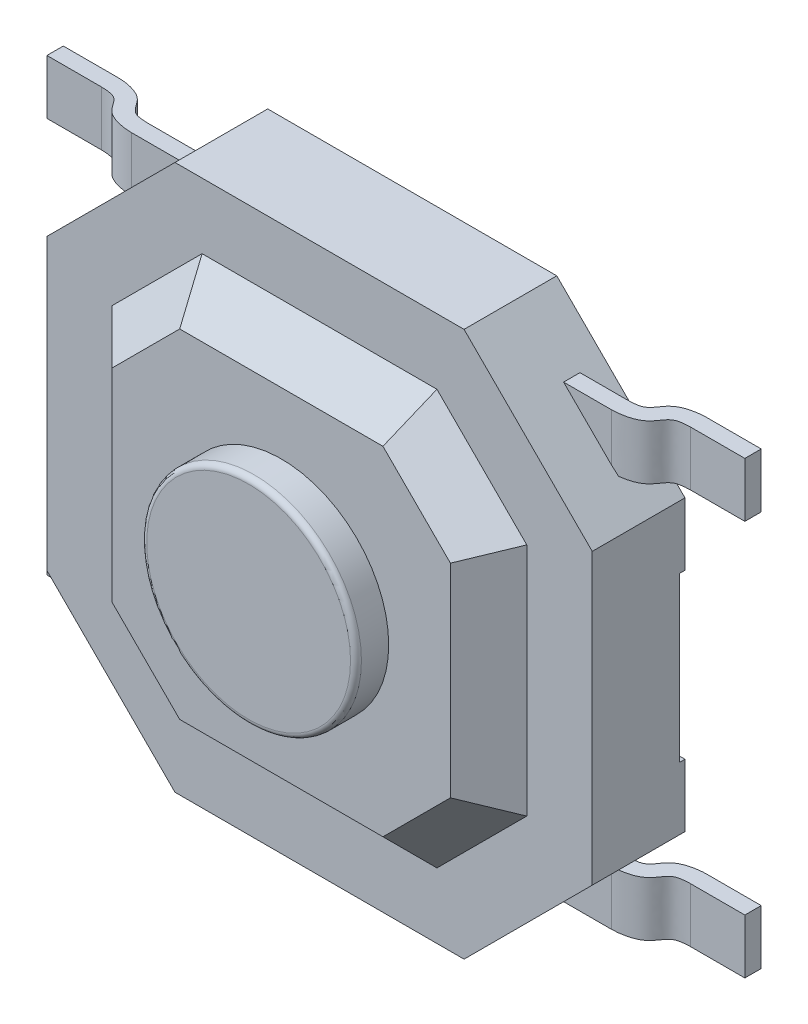
SolidWorks part; units mm, degrees
ref_plane "Front" through (0, 0, 0) normal (0, 0, 1) x (1, 0, 0)
ref_plane "Top" through (0, 0, 0) normal (0, 1, 0) x (1, 0, 0)
ref_plane "Right" through (0, 0, 0) normal (1, 0, 0) x (0, 0, -1)
ref_plane "Plane1" through (0, 0, 0) normal (0, 0, 1) x (1, 0, 0)
sketch "Sketch1" plane through (0, 0, 0) normal (0, 0, 1) x (1, 0, 0)
  line L0 (-1.3462, 2.54) -> (1.3462, 2.54)
  line L1 (1.3462, 2.54) -> (2.54, 1.3462)
  line L2 (2.54, 1.3462) -> (2.54, -1.3462)
  line L3 (2.54, -1.3462) -> (1.3462, -2.54)
  line L4 (1.3462, -2.54) -> (-1.3462, -2.54)
  line L5 (-1.3462, -2.54) -> (-2.54, -1.3462)
  line L6 (-2.54, -1.3462) -> (-2.54, 1.3462)
  line L7 (-2.54, 1.3462) -> (-1.3462, 2.54)
  line L8 (0, 2.54) -> (0, -2.54) construction
  point P10 (0, 0)
  dimension "D1" = 5.08
  dimension "D2" = 5.08
  dimension "D3" = 2.6924
extrude "Base" add sketch "Sketch1" along normal blind 0.8636
sketch "Sketch2" plane through (0, 0, 0.8636) normal (0, 0, 1) x (1, 0, 0)
  line L16 (-1.0937, 1.9304) -> (-1.9304, 1.0937)
  line L17 (-1.9304, 1.0937) -> (-1.9304, -1.0937)
  line L18 (-1.9304, -1.0937) -> (-1.0937, -1.9304)
  line L19 (-1.0937, -1.9304) -> (1.0937, -1.9304)
  line L20 (1.0937, -1.9304) -> (1.9304, -1.0937)
  line L21 (1.9304, -1.0937) -> (1.9304, 1.0937)
  line L22 (1.9304, 1.0937) -> (1.0937, 1.9304)
  line L23 (1.0937, 1.9304) -> (-1.0937, 1.9304)
  line L24 (-1.0937, 1.9304) -> (-1.9304, 1.0937)
  line L25 (-1.9304, 1.0937) -> (-1.9304, -1.0937)
  line L26 (-1.9304, -1.0937) -> (-1.0937, -1.9304)
  line L27 (-1.0937, -1.9304) -> (1.0937, -1.9304)
  line L28 (1.0937, -1.9304) -> (1.9304, -1.0937)
  line L29 (1.9304, -1.0937) -> (1.9304, 1.0937)
  line L30 (1.9304, 1.0937) -> (1.0937, 1.9304)
  line L31 (1.0937, 1.9304) -> (-1.0937, 1.9304)
  dimension "D1" = 0.6096
extrude "Tier1" add sketch "Sketch2" along normal blind 0.3556
chamfer "Chamfer1" distance 0.3556 angle 45 8 edges at (-1.512, 1.512, 1.2192) (0, 1.9304, 1.2192) (1.512, 1.512, 1.2192) (1.9304, 0, 1.2192) (1.512, -1.512, 1.2192) (0, -1.9304, 1.2192) (-1.512, -1.512, 1.2192) (-1.9304, 0, 1.2192) tangent propagation no
sketch "Sketch3" plane through (0, 0, 1.2192) normal (0, 0, 1) x (1, 0, 0)
  circle A0 centre (0, 0) radius 1
  dimension "D1" = 2
extrude "Button" add sketch "Sketch3" along normal blind 0.3048
fillet "ButtonC" radius 0.0508 1 edges at (1, 0, 1.524)
sketch "Sketch4" plane through (0, 0, 0) normal (0, 0, -1) x (-1, 0, 0)
  line L0 (2.54, 1.3462) -> (2.54, -1.3462) construction
  line L1 (2.54, -0.762) -> (-2.54, -0.762)
  line L2 (2.54, -0.762) -> (2.54, 0.762)
  line L3 (2.54, 0.762) -> (-2.54, 0.762)
  line L4 (-2.54, -0.762) -> (-2.54, 0.762)
  line L5 (-2.54, -1.3462) -> (-2.54, 1.3462) construction
  line L6 (0, -0.762) -> (0, 0.762) construction
  point P10 (0, 0)
  dimension "D1" = 1.524
extrude "Bottom cut" cut sketch "Sketch4" against normal blind 0.0508
sketch "Sketch6" plane through (0, -2.54, 0) normal (0, -1, 0) x (1, 0, 0)
  line L1 (-0.8382, 0.381) -> (-2.2352, 0.381)
  line L2 (-0.8382, 0.381) -> (-0.8382, 0.2286)
  line L3 (-0.8382, 0.2286) -> (-2.2352, 0.2286)
  line L4 (-2.2352, 0.381) -> (-2.2352, 0.2286)
  line L5 (-1.3462, 0) -> (1.3462, 0) construction
  line L6 (-1.3462, 0.8636) -> (-1.3462, 0) construction
  line L7 (-3.25, 0) -> (-2.742, 0)
  line L8 (-3.25, 0) -> (-3.25, 0.1524)
  line L9 (-3.25, 0.1524) -> (-2.742, 0.1524)
  line L10 (-2.742, 0) -> (-2.742, 0.1524)
  line L12 (-1.3462, 0.8636) -> (1.3462, 0.8636) construction
  line L13 (-3.0129, 0.0762) -> (-2.4711, 0.0762) construction
  line L14 (-2.5061, 0.3048) -> (-1.9643, 0.3048) construction
  spline S0 degree 3 poles (-2.2352, 0.3048) (-2.5739, 0.3048) (-2.4033, 0.0762) (-2.742, 0.0762) knots 0 0 0 0 1 1 1 1
  spline S1 degree 1 poles (-2.2352, 0.381) (-2.742, 0.1524) knots 0 0 1 1 construction
  spline S2 degree 3 poles (-2.2352, 0.381) (-2.3077, 0.381) (-2.477, 0.3473) (-2.5562, 0.2228) (-2.5912, 0.1832) (-2.642, 0.1591) (-2.7123, 0.1524) (-2.742, 0.1524) knots 0 0 0 0 0.25 0.5 0.75 0.875 1 1 1 1
  spline S3 degree 1 poles (-2.2352, 0.2286) (-2.742, 0) knots 0 0 1 1 construction
  spline S4 degree 3 poles (-2.2352, 0.2286) (-2.2649, 0.2286) (-2.3352, 0.2219) (-2.386, 0.1978) (-2.421, 0.1582) (-2.5002, 0.0337) (-2.6695, 0) (-2.742, 0) knots 0 0 0 0 0.125 0.25 0.5 0.75 1 1 1 1
  point P14 (0, 0.8636)
  point P15 (-5.396, 6.0489)
  line M4 (-1.3462, 0.8636) -> (-1.3462, 0)
  dimension "D9" = 1.016
  dimension "D10" = 1.016
  dimension "D1" = 0.381
  dimension "D2" = 0.1524
  dimension "D3" = 0.508
  dimension "D4" = 3.25
  dimension "D5" = 0.508
  dimension "D6" = 1.397
  dimension "D7" = 0.0762
  dimension "D8" = 0.0762
extrude "pins" add sketch "Sketch6" against normal blind 0.508 from offset 0.4445 contours L3 L2 L1 M4 | L1 L4 L3 M4 | L4 S2 L10 S0 | S4 L4 S0 L10 | L7 L10 L9 L8 region at (-1.0922, -2.54, 0.3048) region at (-1.7907, -2.54, 0.3048) region at (-2.4921, -2.54, 0.2324) region at (-2.4851, -2.54, 0.1486) region at (-2.996, -2.54, 0.0762) offset against normal yes
mirror "pins2" about plane through (0, 0, 0) normal (0, 1, 0) of "pins"
mirror "Mirror2" about plane through (0, 0, 0) normal (1, 0, 0) of "pins2", "pins"
